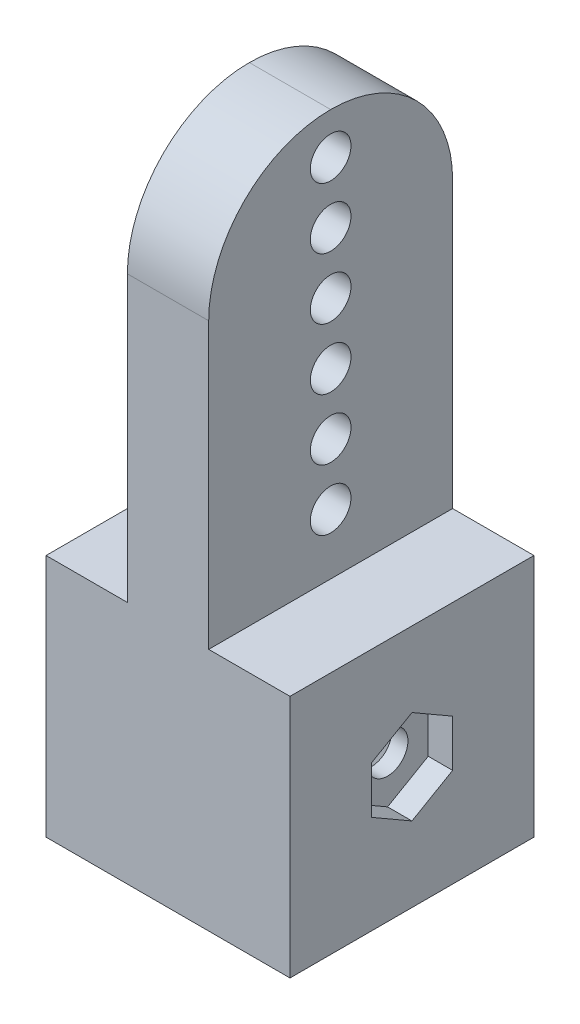
SolidWorks part; units mm, degrees
material "ABS"
ref_plane "Front Plane" through (0, 0, 0) normal (0, 0, 1) x (1, 0, 0)
ref_plane "Top Plane" through (0, 0, 0) normal (0, 1, 0) x (1, 0, 0)
ref_plane "Right Plane" through (0, 0, 0) normal (1, 0, 0) x (0, 0, -1)
sketch "Sketch1" plane through (0, 0, 0) normal (0, 1, 0) x (1, 0, 0)
  line L1 (-10, 10) -> (10, 10)
  line L2 (-10, 10) -> (-10, -10)
  line L3 (-10, -10) -> (10, -10)
  line L4 (10, 10) -> (10, -10)
  line L5 (-10, 10) -> (10, -10) construction
  line L6 (-10, -10) -> (10, 10) construction
  line L7 (-15, 15) -> (15, 15)
  line L8 (-15, 15) -> (-15, -15)
  line L9 (-15, -15) -> (15, -15)
  line L10 (15, 15) -> (15, -15)
  line L11 (-15, 15) -> (15, -15) construction
  line L12 (-15, -15) -> (15, 15) construction
  point P0 (0, 0)
  point P6 (0, 0)
  dimension "D1" = 20
  dimension "D2" = 20
  dimension "D3" = 30
  dimension "D4" = 30
extrude "Boss-Extrude1" add sketch "Sketch1" along normal blind 20
extrude "Boss-Extrude2" add sketch "Sketch1<2>" along normal blind 10 from surface contours L4 L1 L2 L3 | L10 L7 L8 L9 L1 L4 L3 L2 region at (0, 0, 0) region at (0, 0, -14.5757) starting at face at (0, 20, 0)
sketch "Sketch1<2>" plane through (0, 0, 0) normal (0, 1, 0) x (1, 0, 0) same geometry as "Sketch1"
sketch "Sketch3" plane through (15, 0, 0) normal (1, 0, 0) x (0, 0, -1)
  line L1 (0, 9.2265) -> (5, 12.1132)
  line L2 (5, 12.1132) -> (5, 17.8868)
  line L3 (5, 17.8868) -> (0, 20.7735)
  line L4 (0, 20.7735) -> (-5, 17.8868)
  line L5 (-5, 17.8868) -> (-5, 12.1132)
  line L6 (-5, 12.1132) -> (0, 9.2265)
  circle A0 centre (0, 15) radius 2.5
  circle A1 centre (0, 15) radius 5 construction
  circle A2 centre (0, 15) radius 4
  dimension "D1" = 5
extrude "Cut-Extrude1" cut sketch "Sketch3" against normal through all contours A0 region at (15, 15, 0)
extrude "Cut-Extrude2" cut sketch "Sketch3<3>" against normal blind 3 contours L5 L6 L1 L2 L3 L4 A2 | A2 A0 region at (15, 10.8022, 2.4236) region at (15, 15, 3.8869)
sketch "Sketch3<3>" plane through (15, 0, 0) normal (1, 0, 0) x (0, 0, -1) same geometry as "Sketch3"
extrude "Cut-Extrude3" cut sketch "Sketch3<4>" along normal blind 3 from surface contours A2 A0 region at (15, 15, 3.8869) starting at face at (-15, 15, -2.5)
sketch "Sketch3<4>" plane through (15, 0, 0) normal (1, 0, 0) x (0, 0, -1) same geometry as "Sketch3"
sketch "Sketch4" plane through (0, 30, 0) normal (0, 1, 0) x (1, 0, 0)
  line L0 (15, 15) -> (-15, 15) construction
  line L1 (-5, -15) -> (5, -15)
  line L2 (-5, -15) -> (-5, 15)
  line L3 (-5, 15) -> (5, 15)
  line L4 (5, -15) -> (5, 15)
  line L5 (-5, -15) -> (5, 15) construction
  line L6 (-5, 15) -> (5, -15) construction
  point P0 (0, 0)
  dimension "D1" = 10
extrude "Boss-Extrude3" add sketch "Sketch4" along normal blind 50
sketch "Sketch5" plane through (5, 0, 0) normal (1, 0, 0) x (0, 0, -1)
  circle A0 centre (0, 37.4072) radius 2.5
  dimension "D1" = 5
extrude "Cut-Extrude4" cut sketch "Sketch5" against normal through all
pattern_linear "LPattern1" count 6 spacing 7.5 along (0, 1, 0) of "Cut-Extrude4"
fillet "Fillet1" radius 15 2 edges at (0, 80, -15) (0, 80, 15)
